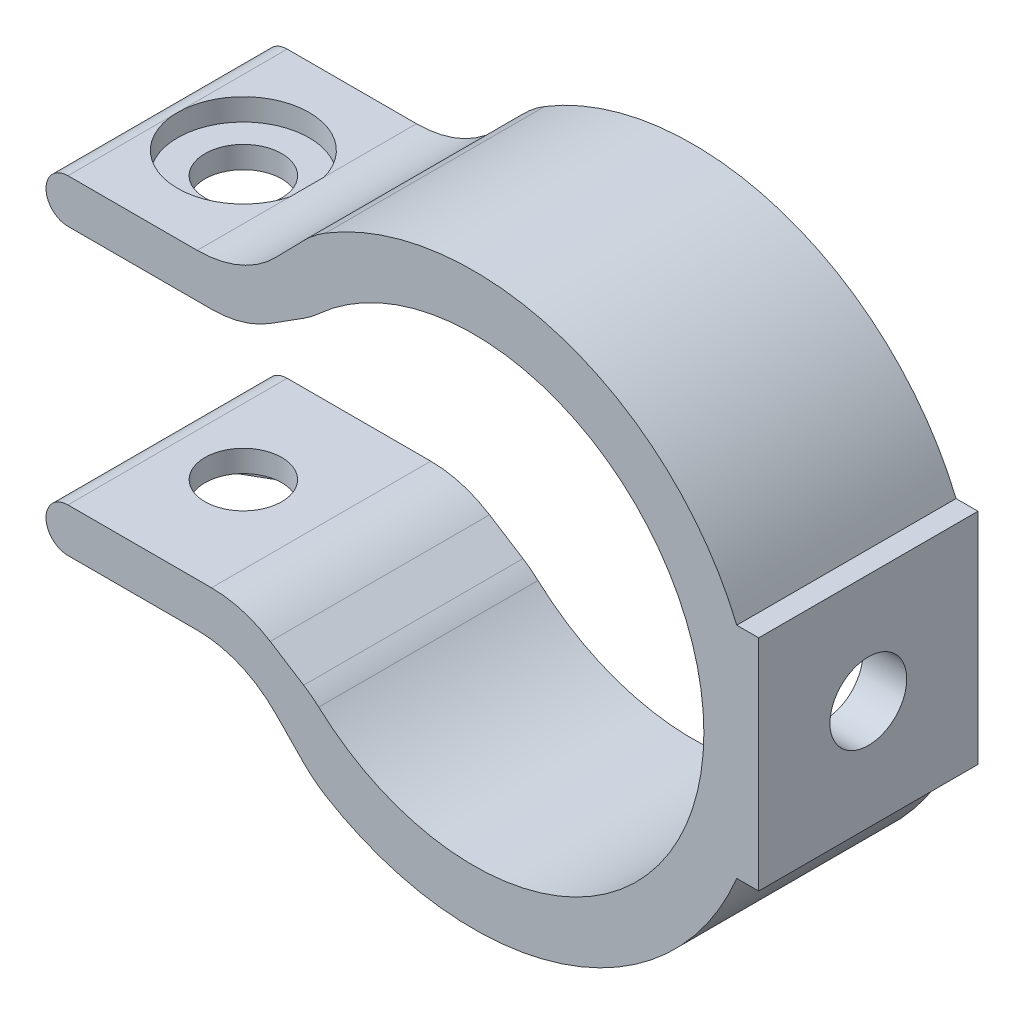
SolidWorks part; units mm, degrees
ref_plane "Спереди" through (0, 0, 0) normal (0, 0, 1) x (1, 0, 0)
ref_plane "Сверху" through (0, 0, 0) normal (0, 1, 0) x (1, 0, 0)
ref_plane "Справа" through (0, 0, 0) normal (1, 0, 0) x (0, 0, -1)
sketch "Эскиз основнной формы" plane through (0, 0, 0) normal (0, 0, 1) x (1, 0, 0)
  line L0 (-7.3485, 2.1487) -> (-7.3485, -8.7626) construction
  line L1 (-10.5, 7.5) -> (-7.3485, 10.7238)
  line L2 (-19.5, 7.5) -> (-10.5, 7.5)
  line L3 (-19.5, 7.5) -> (-19.5, 5.5)
  line L4 (-19.5, 5.5) -> (-10.5, 5.5)
  line L5 (-10.5, 7.5) -> (-10.5, 5.5)
  line L6 (-19.5, 7.5) -> (-10.5, 5.5) construction
  line L7 (-19.5, 5.5) -> (-10.5, 7.5) construction
  line L8 (-10.5, 5.5) -> (-7.3485, 7.5)
  line L9 (-19.5, -5.5) -> (-10.5, -5.5)
  line L10 (-19.5, -5.5) -> (-19.5, -7.5)
  line L11 (-19.5, -7.5) -> (-10.5, -7.5)
  line L13 (-10.5, -5.5) -> (-10.5, -7.5)
  line L14 (-19.5, -5.5) -> (-10.5, -7.5) construction
  line L15 (-19.5, -7.5) -> (-10.5, -5.5) construction
  line L16 (-15, 6.5) -> (-15, -6.5) construction
  line L17 (-7.3485, -7.5) -> (-10.5, -5.5)
  line L18 (-7.3485, -10.7238) -> (-10.5, -7.5)
  arc A0 (-7.3485, -7.5) -> (-7.3485, 7.5) centre (0, 0) ccw
  arc A1 (-7.3485, 10.7238) -> (-7.3485, -10.7238) centre (0, 0) cw
  point P1 (-7.3485, -10.7238)
  point P6 (-15, -6.5)
  point P10 (-15, 6.5)
  point P14 (-7.3485, 10.7238)
  dimension "D1" = 15
  dimension "D5" = 13
  dimension "D8" = 11
  dimension "D7" = 10.5
  dimension "D2" = 2
  dimension "D3" = 9
  dimension "D4" = 15
  dimension "D6" = 2
extrude "Бобышка-Вытянуть1" add sketch "Эскиз основнной формы" along normal blind 5 and the other way blind 5 contours A1 L1 L5 L8 A0 L17 L13 L18 | L5 L2 L3 L4 | L13 L9 L10 L11 region at (-15, 6.5, 0) region at (-8.6736, 8.8669, 0) region at (-15, -6.5, 0)
fillet "Скругление1" radius 5 8 edges at (-7.3485, -10.7238, 0) (-10.5, -7.5, 0) (-7.3485, -7.5, 0) (-10.5, -5.5, 0) (-7.3485, 7.5, 0) (-10.5, 5.5, 0) (-7.3485, 10.7238, 0) (-10.5, 7.5, 0)
fillet "Скругление2" radius 1 4 edges at (-19.5, -7.5, 0) (-19.5, -5.5, 0) (-19.5, 5.5, 0) (-19.5, 7.5, 0)
sketch "Эскиз1" plane through (0, 7.5, 0) normal (0, 1, 0) x (1, 0, 0)
  line L0 (-19.5, -5) -> (-19.5, 5) construction
  circle A0 centre (-15.5, 0) radius 1.75
  circle A1 centre (-15.5, 0) radius 3
  point P8 (-19.5, 0)
  point P11 (-15.5, 0)
  dimension "D1" = 3.5
  dimension "D4" = 6
  dimension "D2" = 4
  dimension "D3" = 5
extrude "Вырез-Вытянуть2" cut sketch "Эскиз1" against normal through all contours A0
extrude "Вырез-Вытянуть3" cut sketch "Эскиз1<6>" against normal blind 1 contours A1
sketch "Эскиз1<6>" plane through (0, 7.5, 0) normal (0, 1, 0) x (1, 0, 0) same geometry as "Эскиз1"
ref_plane "Плоскость2" through (13, 0, 0) normal (1, 0, 0) x (0, 0, -1)
sketch "Эскиз5" plane through (13, 0, 0) normal (1, 0, 0) x (0, 0, -1)
  line L1 (5, -5) -> (-5, -5)
  line L2 (5, -5) -> (5, 5)
  line L3 (5, 5) -> (-5, 5)
  line L4 (-5, -5) -> (-5, 5)
  line L5 (5, -5) -> (-5, 5) construction
  line L6 (5, 5) -> (-5, -5) construction
  point P0 (0, 0)
  dimension "D1" = 10
  dimension "D2" = 10
extrude "Бобышка-Вытянуть2" add sketch "Эскиз5" against normal blind 2
sketch "Эскиз6" plane through (0, 0, 0) normal (1, 0, 0) x (0, 0, -1)
  circle A0 centre (0, 0) radius 1.75
  circle A1 centre (0, 0) radius 3
  dimension "D1" = 3.5
  dimension "D2" = 6
extrude "Вырез-Вытянуть5" cut sketch "Эскиз6" along normal through all contours A0
extrude "Вырез-Вытянуть6" cut sketch "Эскиз6<3>" along normal blind 11 contours A1
sketch "Эскиз6<3>" plane through (0, 0, 0) normal (1, 0, 0) x (0, 0, -1) same geometry as "Эскиз6"
sketch "Эскиз8" plane through (0, -7.5, 0) normal (0, -1, 0) x (1, 0, 0)
  line L0 (-19.5, 5) -> (-19.5, -5) construction
  line L1 (-15.5, 3.4641) -> (-18.5, 1.7321)
  line L2 (-18.5, 1.7321) -> (-18.5, -1.7321)
  line L3 (-18.5, -1.7321) -> (-15.5, -3.4641)
  line L4 (-15.5, -3.4641) -> (-12.5, -1.7321)
  line L5 (-12.5, -1.7321) -> (-12.5, 1.7321)
  line L6 (-12.5, 1.7321) -> (-15.5, 3.4641)
  circle A0 centre (-15.5, 0) radius 3 construction
  dimension "D1" = 6
extrude "Вырез-Вытянуть7" cut sketch "Эскиз8" against normal blind 1
